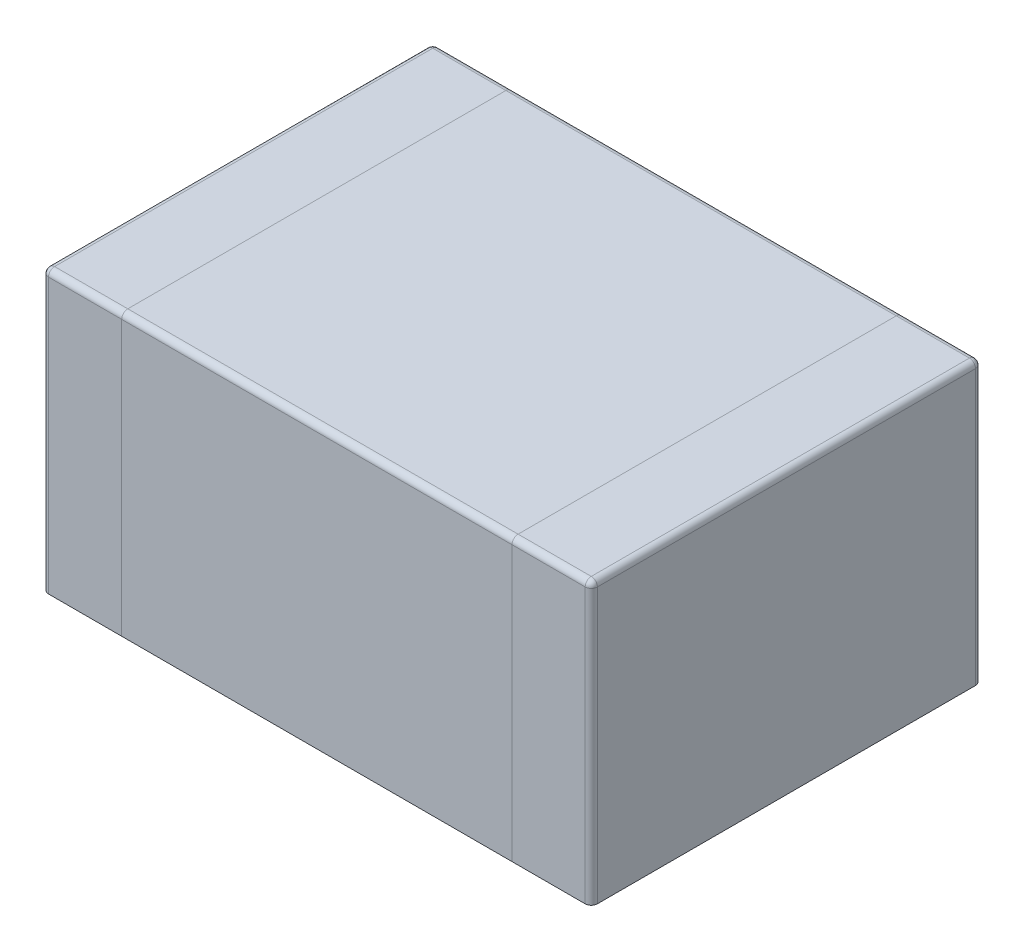
SolidWorks part; units mm, degrees
ref_plane "Alzado" through (0, 0, 0) normal (0, 0, 1) x (1, 0, 0)
ref_plane "Planta" through (0, 0, 0) normal (0, 1, 0) x (1, 0, 0)
ref_plane "Vista lateral" through (0, 0, 0) normal (1, 0, 0) x (0, 0, -1)
sketch "Croquis1" plane through (0, 0, 0) normal (0, 1, 0) x (1, 0, 0)
  line L0 (0, 1.2529) -> (0, -0.9062) construction
  line L1 (2.25, 1.6) -> (-2.25, 1.6)
  line L2 (2.25, 1.6) -> (2.25, -1.6)
  line L3 (2.25, -1.6) -> (-2.25, -1.6)
  line L4 (-2.25, 1.6) -> (-2.25, -1.6)
  line L5 (2.25, 1.6) -> (-2.25, -1.6) construction
  line L6 (2.25, -1.6) -> (-2.25, 1.6) construction
  line L7 (-2.25, 1.6) -> (-1.6, 1.6)
  line L8 (-2.25, 1.6) -> (-2.25, -1.6)
  line L9 (-2.25, -1.6) -> (-1.6, -1.6)
  line L10 (-1.6, 1.6) -> (-1.6, -1.6)
  line L11 (2.25, -1.6) -> (1.6, -1.6)
  line L13 (2.25, 1.6) -> (1.6, 1.6)
  line L14 (2.25, 1.6) -> (2.25, -1.6)
  line L15 (2.25, 1.6) -> (1.6, 1.6)
  line L16 (2.25, 1.6) -> (2.25, -1.6)
  line L17 (2.25, -1.6) -> (1.6, -1.6)
  line L18 (1.6, 1.6) -> (1.6, -1.6)
  point P0 (0, 0)
  dimension "D1" = 4.5
  dimension "D2" = 3.2
  dimension "D3" = 0.65
extrude "Saliente-Extruir1" add sketch "Croquis1" along normal blind 2.3 contours L10 L1 L4 L3 | L1 L18 L3 L2 region at (1.925, 0, 0) region at (-1.925, 0, 0)
sketch "Croquis2" plane through (0, 2.3, 0) normal (0, 1, 0) x (1, 0, 0)
  line L1 (-1.6, 1.6) -> (1.6, 1.6)
  line L2 (-1.6, 1.6) -> (-1.6, -1.6)
  line L3 (-1.6, -1.6) -> (1.6, -1.6)
  line L4 (1.6, 1.6) -> (1.6, -1.6)
extrude "Saliente-Extruir2" add sketch "Croquis2" against normal through all separate body
fillet "Redondeo1" radius 0.05 3 edges at (-1.925, 2.3, -1.6) (-1.925, 2.3, 1.6) (-2.25, 2.3, 0)
fillet "Redondeo2" radius 0.05 2 edges at (0, 2.3, -1.6) (0, 2.3, 1.6)
fillet "Redondeo3" radius 0.05 5 edges at (1.925, 2.3, -1.6) (1.925, 2.3, 1.6) (2.25, 2.3, 0) (2.25, 1.15, 1.6) (2.25, 1.15, -1.6)
fillet "Redondeo4" radius 0.05 4 edges at (-2.2354, 2.2854, 1.5854) (-2.2354, 2.2854, -1.5854) (-2.25, 1.125, 1.6) (-2.25, 1.125, -1.6)
